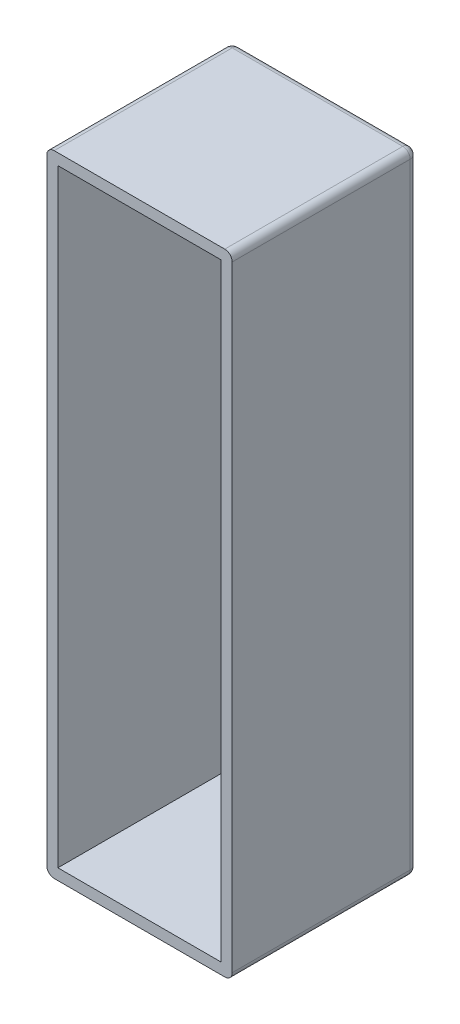
SolidWorks part; units mm, degrees
ref_plane "Front Plane" through (0, 0, 0) normal (0, 0, 1) x (1, 0, 0)
ref_plane "Top Plane" through (0, 0, 0) normal (0, 1, 0) x (1, 0, 0)
ref_plane "Right Plane" through (0, 0, 0) normal (1, 0, 0) x (0, 0, -1)
sketch "Sketch2" plane through (0, 0, 0) normal (0, 0, 1) x (1, 0, 0)
  line L1 (25, 85) -> (-25, 85)
  line L2 (25, 85) -> (25, -85)
  line L3 (25, -85) -> (-25, -85)
  line L4 (-25, 85) -> (-25, -85)
  line L5 (25, 85) -> (-25, -85) construction
  line L6 (25, -85) -> (-25, 85) construction
  point P0 (0, 0)
  dimension "D1" = 50
  dimension "D2" = 170
extrude "Boss-Extrude1" add sketch "Sketch2" along normal blind 50
sketch "Sketch3" plane through (0, 0, 50) normal (0, 0, 1) x (1, 0, 0)
  line L0 (25, 85) -> (-25, 85) construction
  line L1 (-22, 82) -> (22, 82)
  line L2 (-22, 82) -> (-22, -82)
  line L3 (-22, -82) -> (22, -82)
  line L4 (22, 82) -> (22, -82)
  line L5 (-25, -85) -> (25, -85) construction
  line L6 (25, -85) -> (25, 85) construction
  line L7 (-25, 85) -> (-25, -85) construction
  dimension "D1" = 3
  dimension "D2" = 3
  dimension "D3" = 3
  dimension "D4" = 3
extrude "Cut-Extrude1" cut sketch "Sketch3" against normal blind 47
fillet "Fillet2" radius 2 8 edges at (25, -85, 25) (25, 0, 0) (0, -85, 0) (-25, -85, 25) (-25, 0, 0) (25, 85, 25) (0, 85, 0) (-25, 85, 25)
